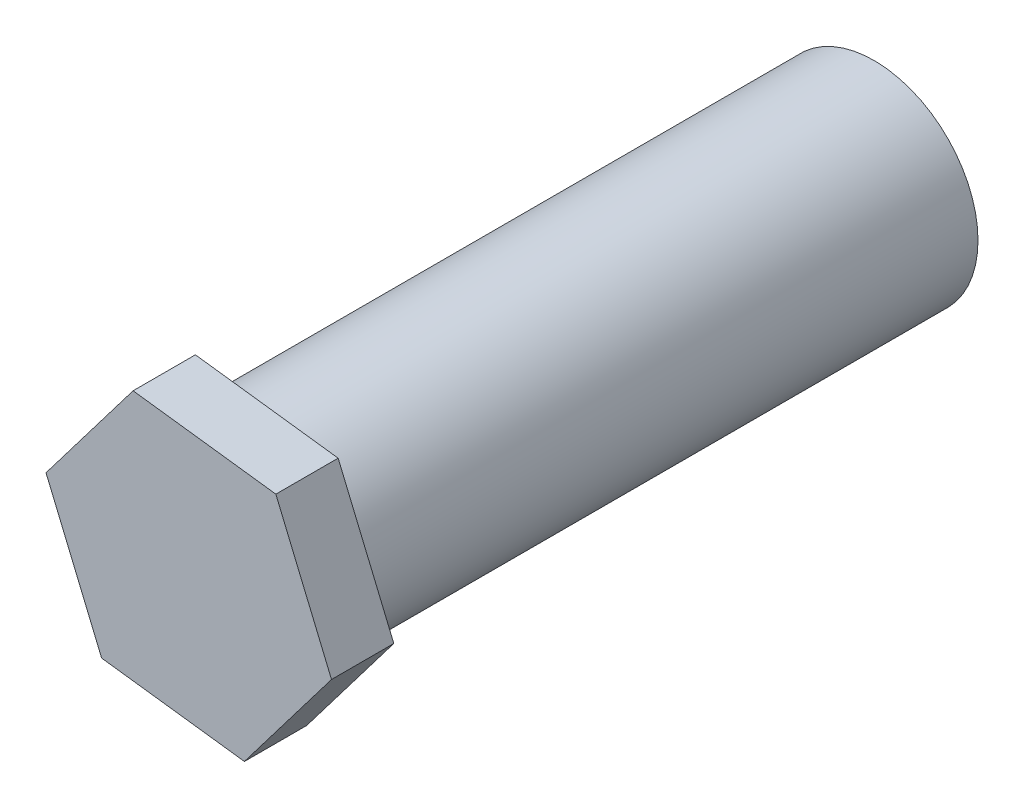
SolidWorks part; units mm, degrees
ref_plane "정면" through (0, 0, 0) normal (0, 0, 1) x (1, 0, 0)
ref_plane "윗면" through (0, 0, 0) normal (0, 1, 0) x (1, 0, 0)
ref_plane "우측면" through (0, 0, 0) normal (1, 0, 0) x (0, 0, -1)
sketch "스케치1" plane through (0, 0, 0) normal (0, 0, 1) x (1, 0, 0)
  circle A0 centre (0, 0) radius 2.5
  dimension "D1" = 5
extrude "보스-돌출1" add sketch "스케치1" along normal blind 15
sketch "스케치2" plane through (0, 0, 15) normal (0, 0, -1) x (-1, 0, 0)
  line L1 (2.0966, -2.7576) -> (3.4364, 0.4369)
  line L2 (3.4364, 0.4369) -> (1.3398, 3.1945)
  line L3 (1.3398, 3.1945) -> (-2.0966, 2.7576)
  line L4 (-2.0966, 2.7576) -> (-3.4364, -0.4369)
  line L5 (-3.4364, -0.4369) -> (-1.3398, -3.1945)
  line L6 (-1.3398, -3.1945) -> (2.0966, -2.7576)
  circle A0 centre (0, 0) radius 3 construction
  circle A1 centre (0, 0) radius 2.5 construction
  dimension "D1" = 0.5
extrude "보스-돌출2" add sketch "스케치2" against normal blind 1.5
